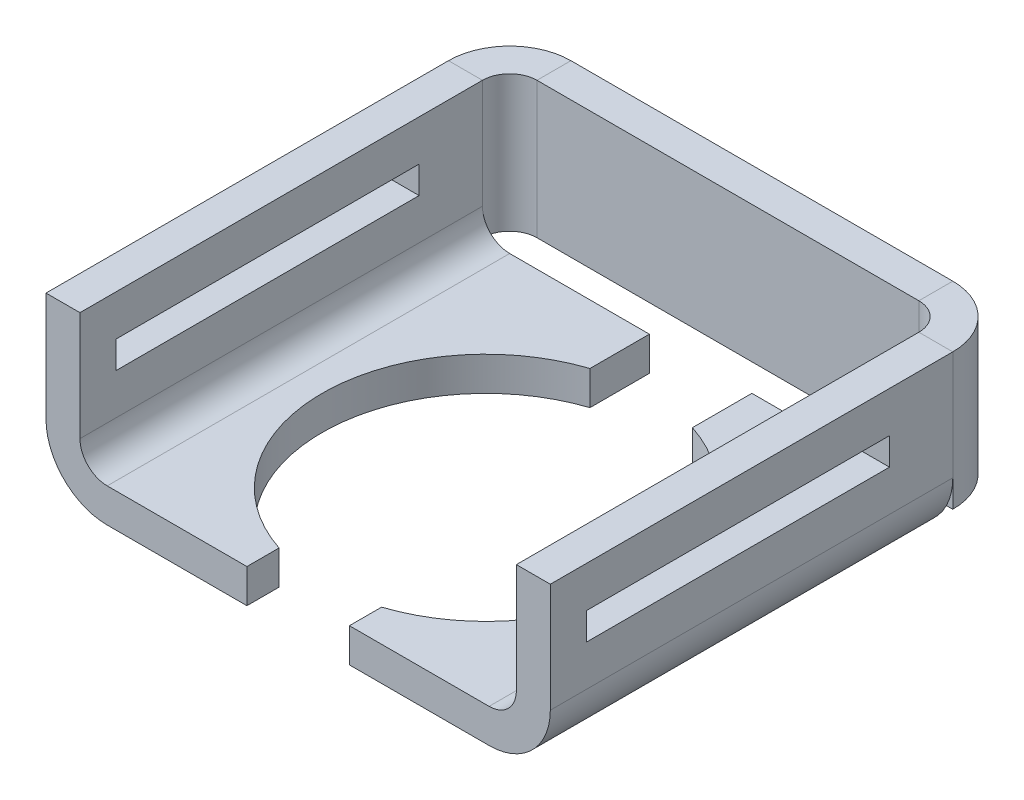
SolidWorks part; units mm, degrees
note: The reader was unsure of these and kept them because the rebuilt part matched: flange length of "Edge-Flange1", "Edge-Flange2".
material "Plain Carbon Steel"
ref_plane "Front Plane" through (0, 0, 0) normal (0, 0, 1) x (1, 0, 0)
ref_plane "Top Plane" through (0, 0, 0) normal (0, 1, 0) x (1, 0, 0)
ref_plane "Right Plane" through (0, 0, 0) normal (1, 0, 0) x (0, 0, -1)
sketch "Sketch1" plane through (0, 0, 0) normal (0, 0, 1) x (1, 0, 0)
  line L1 (-8, 2.5) -> (8, 2.5)
  line L2 (-8, 2.5) -> (-8, -2.5)
  line L3 (-8, -2.5) -> (8, -2.5)
  line L4 (8, 2.5) -> (8, -2.5)
  line L5 (-8, 2.5) -> (8, -2.5) construction
  line L6 (-8, -2.5) -> (8, 2.5) construction
  point P0 (0, 0)
  dimension "D1" = 16
  dimension "D2" = 5
sheet metal parameters "Sheet-Metal1" thickness 1.2446 parameters "D1"=1
base flange "Base-Flange1" sketch "Sketch1" thickness 1.2446 reverse thickness direction no parameters "D1"=1
edge flange "Edge-Flange1" sketch "Sketch7" flange profiles "Sketch7", "Sketch8" flange angle 90 flange length 18 flange position material outside bend radius 1 thickness 1.2446 relief rectangular parameters "D6"=10, "D8"=1
sketch "Sketch7" plane through (8, 0, 0) normal (1, 0, 0) x (0, 1, 0)
  line L2 (-2.5, 0) -> (-2.5, 16.7554)
  line L3 (-2.5, 16.7554) -> (2.5, 16.7554)
  line L4 (2.5, 16.7554) -> (2.5, 0)
  line L5 (-2.5, 0) -> (2.5, 0) construction
  line L6 (-2.5, 0) -> (2.5, 0)
sketch "Sketch8" plane through (-8, 0, 0) normal (-1, 0, 0) x (0, -1, 0)
  line L0 (-2.5, 0) -> (2.5, 0) construction
  line L1 (-2.5, 0) -> (2.5, 0)
  line L2 (-2.5, 0) -> (-2.5, 16.7554)
  line L3 (-2.5, 16.7554) -> (2.5, 16.7554)
  line L4 (2.5, 16.7554) -> (2.5, 0)
bend "EdgeBend1" bend radius 1 bend angle 90 parameters "D5"=1
bend "EdgeBend2" bend radius 1 bend angle 90 parameters "D5"=2
edge flange "Edge-Flange2" sketch "Sketch13" flange profiles "Sketch13", "Sketch14" flange angle 90 flange length 7.366 flange position material outside bend radius 1 thickness 1.2446 relief none parameters "D6"=10, "D8"=1
sketch "Sketch13" plane through (-8, -2.5, 0) normal (0, -1, 0) x (0, 0, -1)
  line L2 (-16.7554, 0) -> (-16.7554, 6.1214)
  line L3 (-16.7554, 6.1214) -> (-1, 6.1214)
  line L4 (-1, 6.1214) -> (-1, 0)
  line L5 (-1, 0) -> (-16.7554, 0) construction
  line L6 (-1, 0) -> (-16.7554, 0)
sketch "Sketch14" plane through (8, -2.5, 0) normal (0, -1, 0) x (0, 0, 1)
  line L0 (16.7554, 0) -> (1, 0) construction
  line L1 (16.7554, 0) -> (1, 0)
  line L2 (1, 0) -> (1, 6.1214)
  line L3 (1, 6.1214) -> (16.7554, 6.1214)
  line L4 (16.7554, 6.1214) -> (16.7554, 0)
bend "EdgeBend3" bend radius 1 bend angle 90 parameters "D5"=3
bend "EdgeBend4" bend radius 1 bend angle 90 parameters "D5"=4
sketch "Sketch15" plane through (0, -2.5, 0) normal (0, 1, 0) x (1, 0, 0)
  line L0 (-7, -1) -> (7, -16.7554) construction
  circle A0 centre (0, -8.8777) radius 6
  dimension "D1" = 12
extrude "Cut-Extrude1" cut sketch "Sketch15" against normal through all normal cut yes
sketch "Sketch16" plane through (9.2446, 0, 0) normal (1, 0, 0) x (0, 0, -1)
  line L0 (-16.7554, 2.5) -> (-1, -1.5) construction
  line L1 (-1, -1.5) -> (-2.4363, -0.8536) construction
  line L3 (-14.434, 0) -> (-3.3215, 0)
  line L4 (-14.434, 0) -> (-14.434, 1)
  line L5 (-14.434, 1) -> (-3.3215, 1)
  line L6 (-3.3215, 0) -> (-3.3215, 1)
  line L7 (-14.434, 0) -> (-3.3215, 1) construction
  line L8 (-14.434, 1) -> (-3.3215, 0) construction
  point P5 (-8.8777, 0.5)
  dimension "D1" = 1
  dimension "D2" = 11.1125
extrude "Cut-Extrude2" cut sketch "Sketch16" against normal through all normal cut yes
sketch "Sketch17" plane through (0, 2.5, 0) normal (0, 1, 0) x (1, 0, 0)
  line L0 (9.2446, -1) -> (9.2446, -16.7554) construction
  line L1 (-9.2446, -16.7554) -> (9.2446, -16.7554)
  line L2 (-9.2446, -16.7554) -> (-9.2446, -15.7554)
  line L3 (-9.2446, -15.7554) -> (9.2446, -15.7554)
  line L4 (9.2446, -16.7554) -> (9.2446, -15.7554)
  dimension "D1" = 1
extrude "Cut-Extrude3" cut sketch "Sketch17" against normal through all normal cut yes
flat pattern "Flat-Pattern1" [suppressed]
sketch "Bend-Lines1" plane through (0, 0, 0) normal (0, 1, 0) x (-1, 0, 0)
bend of the flat pattern "Flatten-<EdgeBend1>1"
bend of the flat pattern "Flatten-<EdgeBend2>1"
bend of the flat pattern "Flatten-<EdgeBend3>1"
bend of the flat pattern "Flatten-<EdgeBend4>1"
